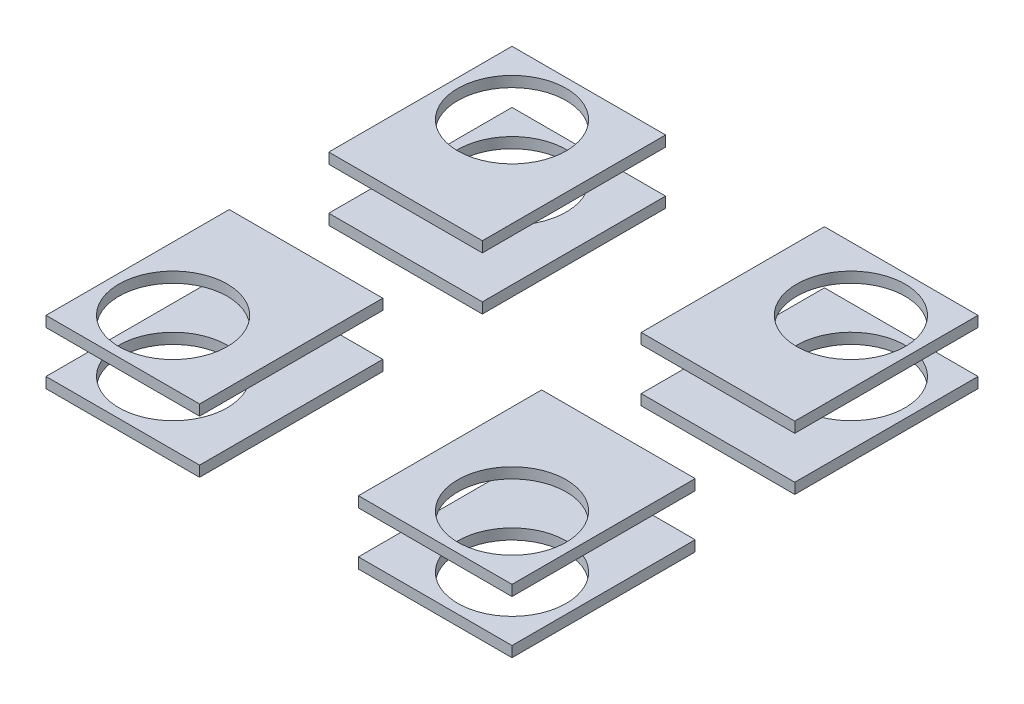
SolidWorks part; units mm, degrees
ref_plane "Front Plane" through (0, 0, 0) normal (0, 0, 1) x (1, 0, 0)
ref_plane "Top Plane" through (0, 0, 0) normal (0, 1, 0) x (1, 0, 0)
ref_plane "Right Plane" through (0, 0, 0) normal (1, 0, 0) x (0, 0, -1)
other "Bounding Box"
ref_plane "Default Plane" through (-8.9266, -12.7485, 0) normal (-0.1736, 0.9848, 0) x (0.9848, 0.1736, 0)
sketch "Sketch1" plane through (0, 0, 0) normal (0, 1, 0) x (1, 0, 0)
  line L0 (-139.7, 101.6) -> (-101.6, 101.6) construction
  line L1 (-139.7, -139.7) -> (139.7, -139.7)
  line L2 (-139.7, -139.7) -> (-139.7, 139.7)
  line L3 (-139.7, 139.7) -> (139.7, 139.7)
  line L4 (139.7, -139.7) -> (139.7, 139.7)
  line L5 (-139.7, -139.7) -> (139.7, 139.7) construction
  line L6 (-139.7, 139.7) -> (139.7, -139.7) construction
  line L7 (-101.6, 101.6) -> (-101.6, 139.7) construction
  line L8 (-38.1, -149.225) -> (-38.1, 149.225)
  line L9 (149.225, -149.225) -> (-149.225, -149.225)
  line L10 (149.225, -149.225) -> (149.225, 149.225)
  line L11 (149.225, 149.225) -> (-149.225, 149.225)
  line L12 (-149.225, -149.225) -> (-149.225, 149.225)
  line L13 (149.225, -149.225) -> (-149.225, 149.225) construction
  line L14 (149.225, 149.225) -> (-149.225, -149.225) construction
  line L15 (38.1, -149.225) -> (38.1, 149.225)
  line L16 (-38.1, 0) -> (0, 0) construction
  line L17 (0, 0) -> (38.1, 0) construction
  line L18 (-101.6, 101.6) -> (-82.55, 50.8)
  line L19 (-82.55, 50.8) -> (-120.65, 50.8)
  line L20 (-101.6, 101.6) -> (-101.6, 50.8) construction
  line L21 (-47.625, -149.225) -> (-47.625, 149.225)
  line L22 (47.625, -149.225) -> (47.625, 149.225)
  line L23 (-47.625, 0) -> (-38.1, 0) construction
  line L24 (38.1, 0) -> (47.625, 0) construction
  line L38 (-139.7, 29.845) -> (139.7, 29.845) construction
  line L39 (-139.7, -29.845) -> (139.7, -29.845) construction
  line L40 (0, -29.845) -> (0, 0) construction
  line L41 (0, 0) -> (0, 29.845) construction
  circle A0 centre (-101.6, 101.6) radius 32.5
  circle A1 centre (-82.55, 50.8) radius 18
  circle A2 centre (-120.65, 50.8) radius 14
  point P0 (0, 0)
  point P9 (0, 0)
  point P29 (0, 0)
  point P34 (0, 0)
  point P48 (93.8022, -8.7646)
  point P50 (-50.8, 6.7403)
  point P51 (0, 0)
  point P52 (-50.8, 8.4926)
  dimension "D3" = 65
  dimension "D6" = 36
  dimension "D7" = 28
  dimension "D1" = 9.525
  dimension "D2" = 38.1
  dimension "D4" = 279.4
  dimension "D5" = 76.2
  dimension "D8" = 38.1
  dimension "D9" = 50.8
  dimension "D10" = 9.525
  dimension "D15" = 20.955
sketch "Sketch2" plane through (0, 0, 0) normal (1, 0, 0) x (0, 0, -1)
  line L0 (0, 0) -> (234.4341, 0) construction
  line L2 (101.6, 25.4) -> (101.6, 92.075) construction
  line L3 (101.6, 50.8) -> (101.6, 53.975)
  line L4 (69.1, 53.975) -> (134.1, 53.975)
  line L5 (69.1, 53.975) -> (69.1, 60.975)
  line L6 (69.1, 60.975) -> (134.1, 60.975)
  line L7 (134.1, 53.975) -> (134.1, 60.975)
  line L8 (69.1, 53.975) -> (134.1, 60.975) construction
  line L9 (69.1, 60.975) -> (134.1, 53.975) construction
  line L10 (69.1, 85.075) -> (134.1, 85.075)
  line L11 (69.1, 85.075) -> (69.1, 92.075)
  line L12 (69.1, 92.075) -> (134.1, 92.075)
  line L13 (134.1, 85.075) -> (134.1, 92.075)
  line L14 (69.1, 85.075) -> (134.1, 92.075) construction
  line L15 (69.1, 92.075) -> (134.1, 85.075) construction
  line L16 (69.1, 60.975) -> (69.1, 73.025)
  line L17 (-139.7, 53.975) -> (139.7, 53.975)
  line L18 (-139.7, 53.975) -> (-139.7, 60.325)
  line L19 (-139.7, 60.325) -> (139.7, 60.325)
  line L20 (139.7, 53.975) -> (139.7, 60.325)
  line L21 (139.7, 85.725) -> (-139.7, 85.725)
  line L22 (139.7, 85.725) -> (139.7, 92.075)
  line L23 (139.7, 92.075) -> (-139.7, 92.075)
  line L24 (-139.7, 85.725) -> (-139.7, 92.075)
  line L33 (149.225, 12.7) -> (139.7, 12.7)
  line L34 (149.225, 12.7) -> (149.225, 101.6)
  line L35 (149.225, 101.6) -> (139.7, 101.6)
  line L36 (139.7, 12.7) -> (139.7, 101.6)
  line L37 (-149.225, 12.7) -> (-139.7, 12.7)
  line L38 (-149.225, 12.7) -> (-149.225, 101.6)
  line L39 (-149.225, 101.6) -> (-139.7, 101.6)
  line L40 (-139.7, 12.7) -> (-139.7, 101.6)
  line L41 (69.1, 73.025) -> (69.1, 85.075)
  circle A0 centre (101.6, 25.4) radius 25.4
  point P3 (101.6, 57.475)
  point P11 (101.6, 88.575)
  point P37 (69.1, 73.025)
  dimension "D1" = 50.8
  dimension "D2" = 7
  dimension "D3" = 65
  dimension "D4" = 3.175
  dimension "D5" = 38.1
  dimension "D6" = 6.35
  dimension "D7" = 9.525
  dimension "D8" = 41.275
ref_plane "Plane1" through (0, 53.975, 0) normal (0, 1, 0) x (1, 0, 0)
sketch "Sketch3" plane through (0, 53.975, 0) normal (0, 1, 0) x (1, 0, 0)
  line L0 (-47.625, -149.225) -> (-47.625, 149.225) construction
  line L1 (-139.7, 139.7) -> (-47.625, 139.7)
  line L2 (-139.7, 139.7) -> (-139.7, 29.845)
  line L3 (-139.7, 29.845) -> (-47.625, 29.845)
  line L4 (-47.625, 139.7) -> (-47.625, 29.845)
  line L5 (-139.7, 29.845) -> (139.7, 29.845) construction
  circle A0 centre (-101.6, 101.6) radius 32.5 construction
  circle A1 centre (-101.6, 101.6) radius 32.5
extrude "Boss-Extrude1" add sketch "Sketch3" along normal up to vertex (6.35 mm away) up to point (0, 60.325, -139.7)
ref_plane "Plane2" through (0, 73.025, 0) normal (0, 1, 0) x (1, 0, 0)
mirror "Mirror1" about plane through (0, 73.025, 0) normal (0, 1, 0) of bodies 104
mirror "Mirror2" about plane through (0, 0, 0) normal (0, 0, 1) of bodies 104 105
mirror "Mirror3" about plane through (0, 0, 0) normal (1, 0, 0) of bodies 106 107 104 105
sketch "Sketch4" plane through (0, 0, 0) normal (1, 0, 0) x (0, 0, -1)
  line L0 (88.9, 114.3) -> (44.3476, 69.85)
  line L1 (44.3476, 69.85) -> (-152.4, 69.85)
  line L2 (-152.4, 6.35) -> (-152.4, 0) construction
  line L3 (149.225, 0) -> (-149.225, 0) construction
  line L4 (139.7, 12.7) -> (139.7, 101.6) construction
  line L5 (-200000, 0) -> (200234.4341, 0) construction
  line L6 (44.3476, 63.5) -> (44.3476, 69.85) construction
  line L7 (77.1137, 31.75) -> (114.3, 56.1013)
  line L8 (114.3, 56.1013) -> (88.9, 114.3)
  line L9 (-152.4, 69.85) -> (44.3476, 63.5)
  circle A0 centre (88.9, 114.3) radius 6.35
  circle A1 centre (-152.4, 69.85) radius 63.5
  circle A2 centre (77.1137, 31.75) radius 20.5
  circle A3 centre (114.3, 56.1013) radius 21
  circle A5 centre (44.3476, 63.5) radius 17.78
  point P17 (114.5245, 63.8857)
  dimension "D1" = 12.7
  dimension "D2" = 127
  dimension "D7" = 41
  dimension "D8" = 42
  dimension "D10" = 35.56
  dimension "D3" = 6.35
  dimension "D4" = 50.8
  dimension "D5" = 114.3
  dimension "D6" = 196.85
  dimension "D9" = 241.3
  dimension "D11" = 6.35
  dimension "D12" = 25.4
  dimension "D13" = 63.5
  dimension "D14" = 31.75
  dimension "D15" = 44.45
sketch "Sketch6" plane through (0, 0, 0) normal (0, 1, 0) x (1, 0, 0)
  line L1 (-23.0411, 101.6113) -> (38.1, 101.6113)
  line L2 (-23.0411, 101.6113) -> (-23.0411, 76.0653)
  line L3 (-23.0411, 76.0653) -> (38.1, 76.0653)
  line L4 (38.1, 101.6113) -> (38.1, 76.0653)
  line L5 (-23.0411, 101.6113) -> (38.1, 76.0653) construction
  line L6 (-23.0411, 76.0653) -> (38.1, 101.6113) construction
  line L8 (-29.573, 133.8479) -> (17.8695, 133.8479)
  line L9 (-29.573, 133.8479) -> (-29.573, 110.7349)
  line L10 (-29.573, 110.7349) -> (17.8695, 110.7349)
  line L11 (17.8695, 133.8479) -> (17.8695, 110.7349)
  line L12 (-29.573, 133.8479) -> (17.8695, 110.7349) construction
  line L13 (-29.573, 110.7349) -> (17.8695, 133.8479) construction
  point P0 (7.5295, 88.8383)
  point P5 (-5.8518, 122.2914)
